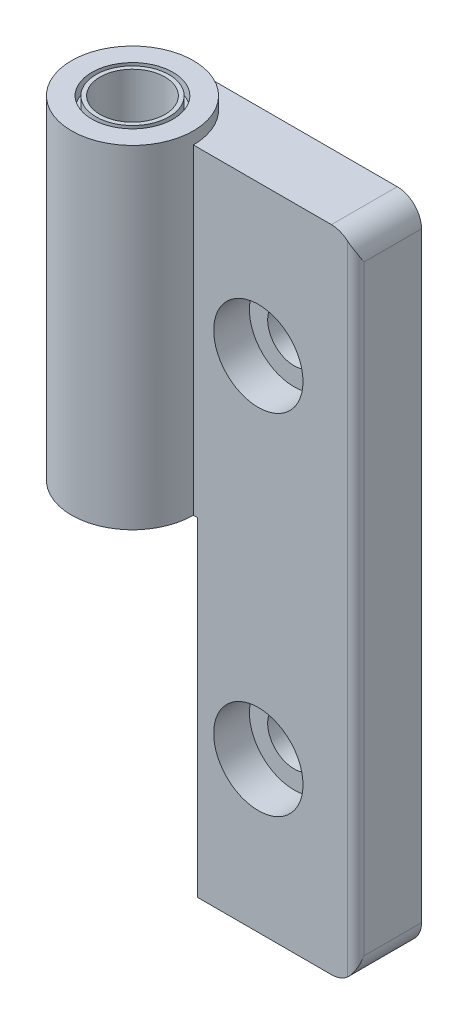
SolidWorks part; units mm, degrees
material "6063-T5"
ref_plane "Piano frontale" through (0, 0, 0) normal (0, 0, 1) x (1, 0, 0)
ref_plane "Piano superiore" through (0, 0, 0) normal (0, 1, 0) x (1, 0, 0)
ref_plane "Piano destro" through (0, 0, 0) normal (1, 0, 0) x (0, 0, -1)
ref_plane "Plane1" through (0, 40, 0) normal (0, 1, 0) x (1, 0, 0)
sketch "Sketch1" plane through (0, 40, 0) normal (0, 1, 0) x (1, 0, 0)
  line L0 (27.5, 8.1) -> (2, 8.1)
  line L1 (2, 8.1) -> (2, 7.2284)
  line L2 (7.5, 0) -> (27.5, 0)
  line L3 (27.5, 0) -> (27.5, 8.1)
  arc A0 (2, 7.2284) -> (7.5, 0) centre (0, 0) ccw
extrude "Extrude1" add sketch "Sketch1" against normal blind 39.5
sketch "Sketch2" plane through (0, 0.5, 0) normal (0, -1, 0) x (1, 0, 0)
  line L0 (27.5, -8.1) -> (8, -8.1)
  line L1 (8, -8.1) -> (8, 0)
  line L2 (8, 0) -> (27.5, 0)
  line L3 (27.5, 0) -> (27.5, -8.1)
extrude "Extrude2" add sketch "Sketch2" along normal blind 40.5
sketch "Sketch3" plane through (0, 40, 0) normal (0, 1, 0) x (-1, 0, 0)
  circle A0 centre (0, 0) radius 7.5
extrude "Extrude3" add sketch "Sketch3" along normal blind 1.5
hole_wizard "HoleWzd1" positions "Sketch5" profile "Sketch4" hole size "Ø10.0" standard "Ansi Metric"
sketch "Sketch5" plane through (0, 41.5, 0) normal (0, 1, 0) x (1, 0, 0)
  point P0 (0, 0)
sketch "Sketch4" plane through (0, 41.5, 0) normal (1, 0, 0) x (0, 0, 1)
  line L0 (0, 0) -> (0, 1.5)
  line L1 (0, 1.5) -> (5, 1.5)
  line L2 (5, 1.5) -> (5, 0)
  line L5 (5, 0) -> (0, 0)
  line L10 (0, 1.5) -> (-5, 1.5) construction
  line L11 (0, -6.35) -> (0, 107.95) construction
  dimension "Hole Dia." = 10
  dimension "Hole Depth" = 1.5
  dimension "Drill Angle" = 180
ref_plane "Plane2" through (0, 0, 0) normal (0, 0, -1) x (-1, 0, 0)
sketch "Sketch6" plane through (0, 0, 0) normal (0, 0, -1) x (-1, 0, 0)
  line L0 (-4.5, 40) -> (0, 40)
  line L1 (0, 40) -> (0, 41.5)
  line L2 (0, 41.5) -> (-4.5, 41.5)
  line L3 (-4.5, 41.5) -> (-4.5, 40)
  line L4 (0, 40) -> (0, 41.5) construction
revolve "Revolve1" add sketch "Sketch6" angle 360 about L4 reverse direction yes
hole_wizard "HoleWzd2" positions "Sketch8" profile "Sketch7" hole size "Ø8.0" standard "Ansi Metric"
sketch "Sketch8" plane through (0, 41.5, 0) normal (0, 1, 0) x (1, 0, 0)
  point P0 (0, 0)
sketch "Sketch7" plane through (0, 41.5, 0) normal (1, 0, 0) x (0, 0, 1)
  line L0 (0, 0) -> (0, 81.5)
  line L1 (0, 81.5) -> (4, 81.5)
  line L2 (4, 81.5) -> (4, 0)
  line L5 (4, 0) -> (0, 0)
  line L11 (0, -6.35) -> (0, 107.95) construction
  dimension "Thru Hole Dia." = 8
  dimension "Thru Hole Depth" = 81.5
hole_wizard "HoleWzd3" positions "Sketch10" profile "Sketch9" counterbore size "M6" standard "Ansi Metric"
sketch "Sketch10" plane through (0, 0, 0) normal (0, 0, 1) x (1, 0, 0)
  point P0 (15.5, 21.5)
  point P1 (15.5, -21.5)
sketch "Sketch9" plane through (15.5, 21.5, 0) normal (1, 0, 0) x (0, -1, 0)
  line L0 (0, 0) -> (0, 8.1)
  line L1 (0, 8.1) -> (3.25, 8.1)
  line L3 (3.25, 8.1) -> (3.25, 4.4)
  line L4 (3.25, 4.4) -> (5.5, 4.4)
  line L5 (5.5, 4.4) -> (5.5, 0)
  line L7 (5.5, 0) -> (0, 0)
  line L11 (0, -6.35) -> (0, 107.95) construction
  dimension "Thru Hole Dia." = 6.5
  dimension "Thru Hole Depth" = 8.1
  dimension "C'Bore Dia." = 11
  dimension "C'Bore Depth" = 4.4
fillet "Fillet1" radius 1 1 edges at (27.5, 0, 0) tangent propagation no
fillet "Fillet2" radius 3 2 edges at (27.5, 40, -4.55) (27.5, -40, -4.55) tangent propagation no
